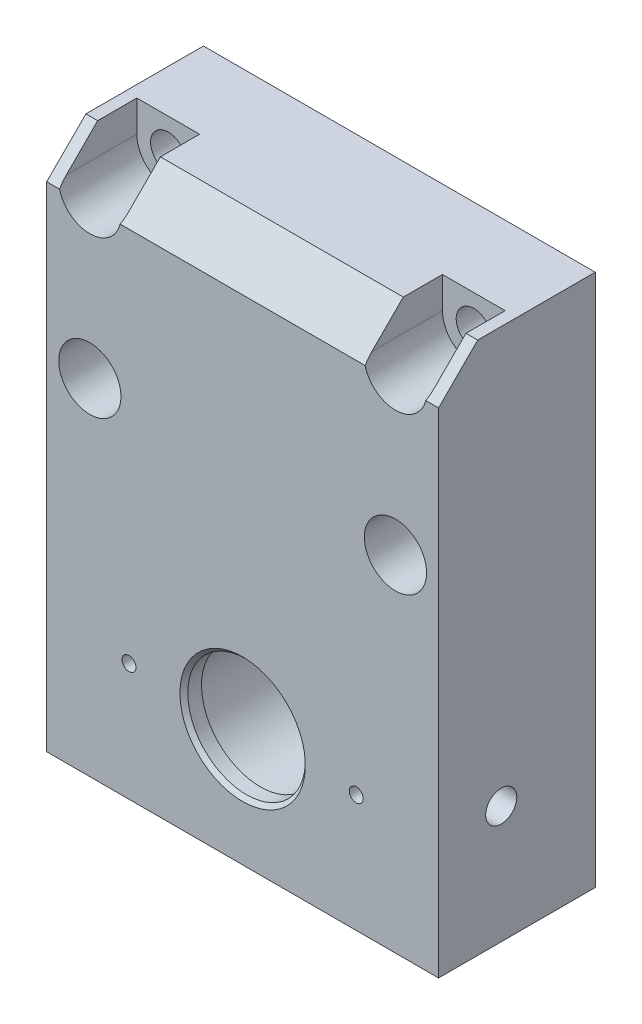
SolidWorks part; units mm, degrees
material "AISI 316 Annealed Stainless Steel Bar (SS)"
ref_plane "Front" through (0, 0, 0) normal (0, 0, 1) x (1, 0, 0)
ref_plane "Top" through (0, 0, 0) normal (0, 1, 0) x (1, 0, 0)
ref_plane "Right" through (0, 0, 0) normal (1, 0, 0) x (0, 0, -1)
sketch "Sketch1" plane through (0, 0, 0) normal (0, 0, 1) x (1, 0, 0)
  line L0 (0, 53) -> (0, 0) construction
  line L1 (-25, -15) -> (25, -15)
  line L2 (-25, -15) -> (-25, 53)
  line L3 (-25, 53) -> (25, 53)
  line L4 (25, -15) -> (25, 53)
  circle A0 centre (0, 0) radius 9.5 construction
  dimension "D3" = 19
  dimension "D5" = 15
  dimension "D1" = 68
  dimension "D2" = 50
extrude "Boss-Extrude1" add sketch "Sketch1" along normal blind 20
sketch "Sketch3" plane through (0, 0, 0) normal (1, 0, 0) x (0, 0, -1)
  line L0 (0, 0) -> (-20, 0)
  line L1 (-20, 0) -> (-20, 7.5)
  line L2 (-20, 7.5) -> (-17.75, 7.5)
  line L3 (-17.75, 7.5) -> (-17.75, 8)
  line L4 (-17.75, 8) -> (-7, 8)
  line L5 (-7, 8) -> (-7, 11)
  line L6 (-7, 11) -> (0, 11)
  line L7 (0, 53) -> (0, 0) construction
  line L8 (0, 11) -> (0, 0)
  line L9 (-20, -15) -> (-20, 53) construction
  dimension "D1" = 11
  dimension "D2" = 8
  dimension "D3" = 7.5
  dimension "D4" = 7
  dimension "D5" = 2.25
revolve "Cut-Revolve1" cut sketch "Sketch3" angle 360 about L0
hole_wizard "5/32 (0.15625) Diameter Hole1" positions "Sketch4" profile "Sketch5" hole size "5/32" standard "ANSI Inch" end condition up to next
sketch "Sketch4" plane through (25, 0, 0) normal (1, 0, 0) x (0, 0, -1)
  line L1 (0, 0) -> (-20, 0) construction
  line L2 (-20, -15) -> (-20, 53) construction
  point P0 (-12, 0)
  dimension "D1" = 8
sketch "Sketch5" plane through (25, 0, 12) normal (0, 1, 0) x (0, 0, -1)
  line L0 (0, 0) -> (0, 17)
  line L1 (0, 17) -> (1.9844, 17)
  line L2 (1.9844, 17) -> (1.9844, 0)
  line L5 (1.9844, 0) -> (0, 0)
  line L11 (0, -6.35) -> (0, 107.95) construction
  dimension "Thru Hole Dia." = 3.9688
  dimension "Thru Hole Depth" = 17
fillet "Fillet1" radius 5 1 edges at (0, 53, 20) profile chamfer
hole_wizard "#2-56 Tapped Hole1" positions "Sketch8" profile "Sketch9" tap size "#2-56" standard "ANSI Inch"
sketch "Sketch8" plane through (0, 0, 20) normal (0, 0, 1) x (1, 0, 0)
  line L0 (-14.5, 0) -> (14.5, 0)
  point P0 (-14.5, 0)
  point P2 (14.5, 0)
  dimension "D1" = 29
sketch "Sketch9" plane through (-14.5, 0, 20) normal (1, 0, 0) x (0, -1, 0)
  line L0 (0, 0) -> (0, 8.4542)
  line L1 (0, 8.4542) -> (0.889, 7.92)
  line L2 (0.889, 7.92) -> (0.889, 0)
  line L5 (0.889, 0) -> (0, 0)
  line L10 (0, 8.4542) -> (-0.889, 7.92) construction
  line L11 (0, -6.35) -> (0, 107.95) construction
  dimension "Tap Drill Dia." = 1.778
  dimension "Tap Drill Depth" = 7.92
  dimension "Drill Angle" = 118
cosmetic thread "Hole Thread1" parameters "D1"=6.2259, "D2"=2.1844
cosmetic thread "Hole Thread2" parameters "D1"=6.555, "D2"=2.1844
sketch "Sketch19" plane through (0, 0, 20) normal (0, 0, 1) x (1, 0, 0)
  line L0 (23.5, 53) -> (23.5, 49)
  line L1 (15.5, 49) -> (15.5, 53)
  line L2 (15.5, 53) -> (23.5, 53)
  line L3 (0, 0) -> (0, 48) construction
  line L4 (25, 48) -> (-25, 48) construction
  line L6 (-25, 53) -> (25, 53) construction
  line L7 (-15.5, 53) -> (-23.5, 53)
  line L8 (-15.5, 49) -> (-15.5, 53)
  line L9 (-23.5, 53) -> (-23.5, 49)
  line L10 (25, 53) -> (25, 48) construction
  arc A0 (23.5, 49) -> (15.5, 49) centre (19.5, 49) cw
  arc A1 (-23.5, 49) -> (-15.5, 49) centre (-19.5, 49) ccw
  dimension "D3" = 4
  dimension "D1" = 5.5
  dimension "D2" = 4
extrude "Cut-Extrude2" cut sketch "Sketch19" against normal blind 10
hole_wizard "#8 Clearance Hole1" positions "Sketch20" profile "Sketch21" hole size "#8" standard "ANSI Inch" end condition through all
sketch "Sketch20" plane through (0, 0, 10) normal (0, 0, 1) x (1, 0, 0)
  point P0 (19.5, 49)
  point P5 (-19.5, 49)
sketch "Sketch21" plane through (19.5, 49, 10) normal (1, 0, 0) x (0, -1, 0)
  line L0 (0, 0) -> (0, 10)
  line L1 (0, 10) -> (2.2479, 10)
  line L2 (2.2479, 10) -> (2.2479, 0)
  line L5 (2.2479, 0) -> (0, 0)
  line L11 (0, -6.35) -> (0, 107.95) construction
  dimension "Thru Hole Dia." = 4.4958
  dimension "Thru Hole Depth" = 10
hole_wizard "CBORE for #8 Socket Head Cap Screw1" positions "Sketch16" profile "Sketch17" counterbore size "#8" standard "ANSI Inch" end condition through all
sketch "Sketch16" plane through (0, 0, 20) normal (0, 0, 1) x (1, 0, 0)
  line L0 (-19.5, 29) -> (-19.5, 49) construction
  line L1 (-19.5, 49) -> (19.5, 49) construction
  line L2 (19.5, 49) -> (19.5, 29) construction
  line L5 (0, 49) -> (0, 53) construction
  line L8 (-25, 48) -> (-25, -15) construction
  line L9 (-15.5, 53) -> (15.5, 53) construction
  point P0 (-19.5, 29)
  point P6 (19.5, 29)
  dimension "D1" = 5.5
  dimension "D2" = 4
  dimension "D3" = 20
sketch "Sketch17" plane through (-19.5, 29, 20) normal (1, 0, 0) x (0, -1, 0)
  line L0 (0, 0) -> (0, 20)
  line L1 (0, 20) -> (2.2479, 20)
  line L3 (2.2479, 20) -> (2.2479, 10)
  line L4 (2.2479, 10) -> (3.9687, 10)
  line L5 (3.9687, 10) -> (3.9687, 0)
  line L7 (3.9687, 0) -> (0, 0)
  line L11 (0, -6.35) -> (0, 107.95) construction
  dimension "Thru Hole Dia." = 4.4958
  dimension "Thru Hole Depth" = 20
  dimension "C'Bore Dia." = 7.9375
  dimension "C'Bore Depth" = 10
hole_wizard "1/8 (0.1250) Dowel Hole1" positions "Sketch10" profile "Sketch11" hole size "1/8" standard "ANSI Inch"
sketch "Sketch10" plane through (0, 0, 0) normal (0, 0, -1) x (-1, 0, 0)
  line L10 (-19.5, 49) -> (-19.5, 29) construction
  point P0 (-19.5, 39)
sketch "Sketch11" plane through (19.5, 39, 0) normal (1, 0, 0) x (0, 1, 0)
  line L0 (0, 0) -> (0, 5.9539)
  line L1 (0, 5.9539) -> (1.5875, 5)
  line L2 (1.5875, 5) -> (1.5875, 0)
  line L5 (1.5875, 0) -> (0, 0)
  line L10 (0, 5.9539) -> (-1.5875, 5) construction
  line L11 (0, -6.35) -> (0, 107.95) construction
  dimension "Hole Dia." = 3.175
  dimension "Hole Depth" = 5
  dimension "Drill Angle" = 118
hole_wizard "1/8 (0.1250) Dowel Slot1" positions "Sketch12" profile "Sketch13" size "1/8" standard "ANSI Inch" slot yes
sketch "Sketch12" plane through (0, 0, 0) normal (0, 0, -1) x (-1, 0, 0)
  line L0 (17.5, 39) -> (21.5, 39) construction
  line L5 (19.5, 29) -> (19.5, 49) construction
  point P0 (19.5, 39)
  dimension "D1" = 4
sketch "Sketch13" plane through (-19.5, 39, 0) normal (1, 0, 0) x (0, 1, 0)
  line L0 (0, 0) -> (0, 5.9539)
  line L1 (0, 5.9539) -> (1.5875, 5)
  line L2 (1.5875, 5) -> (1.5875, 0)
  line L5 (1.5875, 0) -> (0, 0)
  line L10 (0, 5.9539) -> (-1.5875, 5) construction
  line L11 (0, -6.35) -> (0, 107.95) construction
  dimension "Hole Dia." = 3.175
  dimension "Hole Depth" = 5
  dimension "Drill Angle" = 118
sketch "Sketch22" plane through (0, 0, 0) normal (0, 0, -1) x (-1, 0, 0)
  circle A0 centre (0, 0) radius 10
  dimension "D1" = 20
extrude "Cut-Extrude3" [suppressed] cut sketch "Sketch22" along normal blind 1.1 from offset 2 offset against normal yes
chamfer "Chamfer1" distance 0.5 angle 45 2 edges at (0, 11, 0) (0, 7.5, 20)
